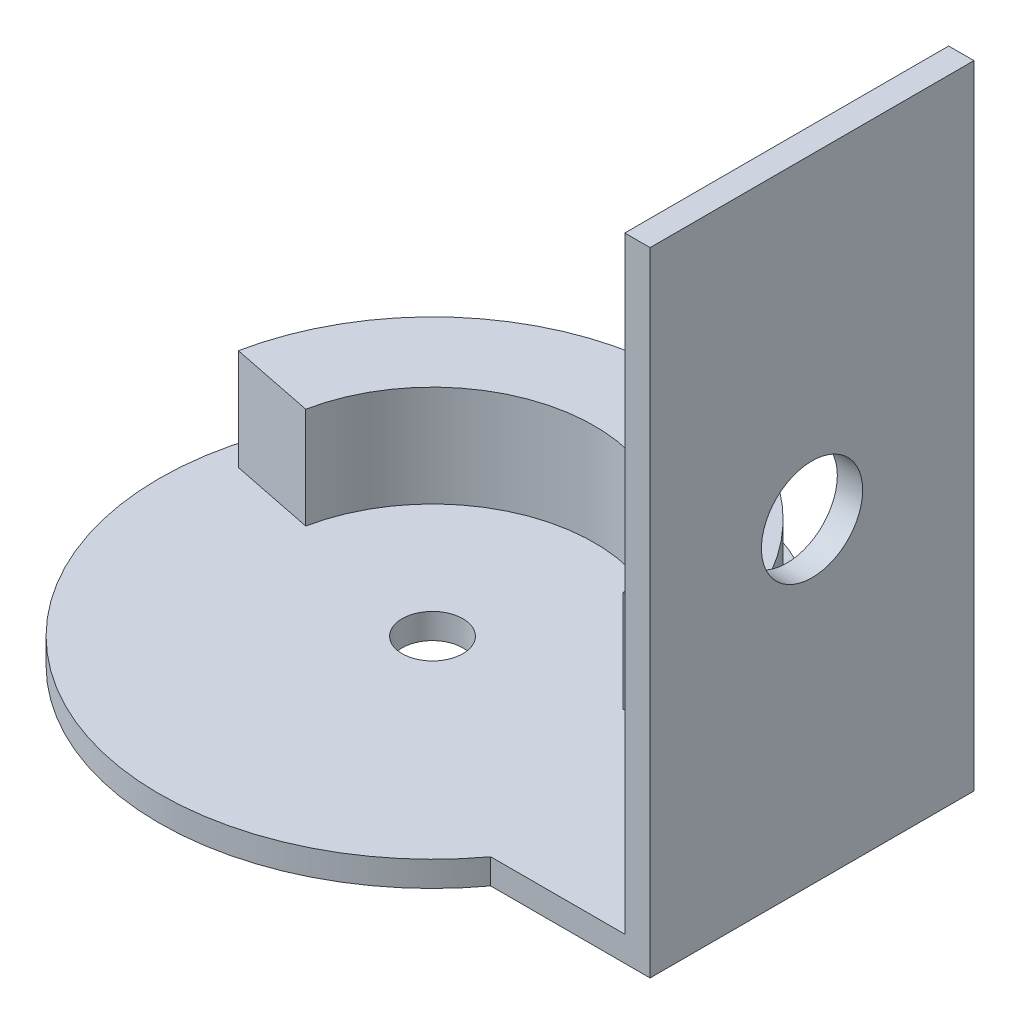
SolidWorks part; units mm, degrees
ref_plane "Front Plane" through (0, 0, 0) normal (0, 0, 1) x (1, 0, 0)
ref_plane "Top Plane" through (0, 0, 0) normal (0, 1, 0) x (1, 0, 0)
ref_plane "Right Plane" through (0, 0, 0) normal (1, 0, 0) x (0, 0, -1)
sketch "Sketch1" plane through (0, 0, 0) normal (0, 1, 0) x (1, 0, 0)
  line L0 (-55, 0) -> (55, 0) construction
  line L1 (-24.0173, 4.8395) -> (-20.7184, 21.2108) construction
  line L2 (-24.0173, 4.8395) -> (-15.6847, 3.1605)
  line L3 (0, -55) -> (0, 55) construction
  line L4 (24.0173, 4.8395) -> (15.6847, 3.1605)
  line L5 (-23.9844, 5) -> (23.9844, 5) construction
  circle A0 centre (0, 0) radius 16 construction
  circle A1 centre (0, 0) radius 24.5 construction
  arc A2 (-24.0173, 4.8395) -> (24.0173, 4.8395) centre (0, 0) cw
  arc A3 (-15.6847, 3.1605) -> (15.6847, 3.1605) centre (0, 0) cw
  point P20 (-19.851, 4)
  dimension "D1" = 32
  dimension "D2" = 49
  dimension "D3" = 1
  dimension "D4" = 5
extrude "Boss-Extrude1" add sketch "Sketch1" along normal blind 10 contours A2 L4 A3 L2
sketch "Sketch2" plane through (0, 0, 0) normal (0, -1, 0) x (1, 0, 0)
  line L1 (37.5, -16) -> (37.5, 16)
  line L3 (21.7486, -16) -> (37.5, -16)
  line L5 (21.7486, 16) -> (37.5, 16)
  line L6 (0, -55) -> (0, 55) construction
  circle A1 centre (0, 0) radius 27 construction
  circle A2 centre (0, 0) radius 3
  arc A3 (0, -27) -> (0, 27) centre (0, 0) cw
  circle A4 centre (0, 0) radius 16 construction
  arc A5 (21.7486, -16) -> (0, -27) centre (0, 0) cw
  arc A6 (0, 27) -> (21.7486, 16) centre (0, 0) cw
  dimension "D1" = 54
  dimension "D2" = 6
  dimension "D3" = 37.5
extrude "Boss-Extrude2" add sketch "Sketch2" along normal blind 2.5
sketch "Sketch4" plane through (0, 0, 0) normal (0, 1, 0) x (1, 0, 0)
  line L0 (37.5, -16) -> (21.7486, -16) construction
  line L1 (37.5, -16) -> (35, -16)
  line L2 (37.5, -16) -> (37.5, 16)
  line L3 (37.5, 16) -> (35, 16)
  line L4 (35, -16) -> (35, 16)
  line L5 (21.7486, 16) -> (37.5, 16) construction
  dimension "D1" = 2.5
  dimension "D2" = 35
extrude "Boss-Extrude3" add sketch "Sketch4" along normal blind 60
sketch "Sketch5" plane through (37.5, 0, 0) normal (1, 0, 0) x (0, 0, -1)
  line L0 (16, 60) -> (-16, -2.5) construction
  line L1 (-16, -2.5) -> (16, -2.5) construction
  line L2 (16, -2.5) -> (-16, 60) construction
  circle A0 centre (0, 28.75) radius 5
  dimension "D1" = 10
extrude "Cut-Extrude1" cut sketch "Sketch5" against normal blind 10
